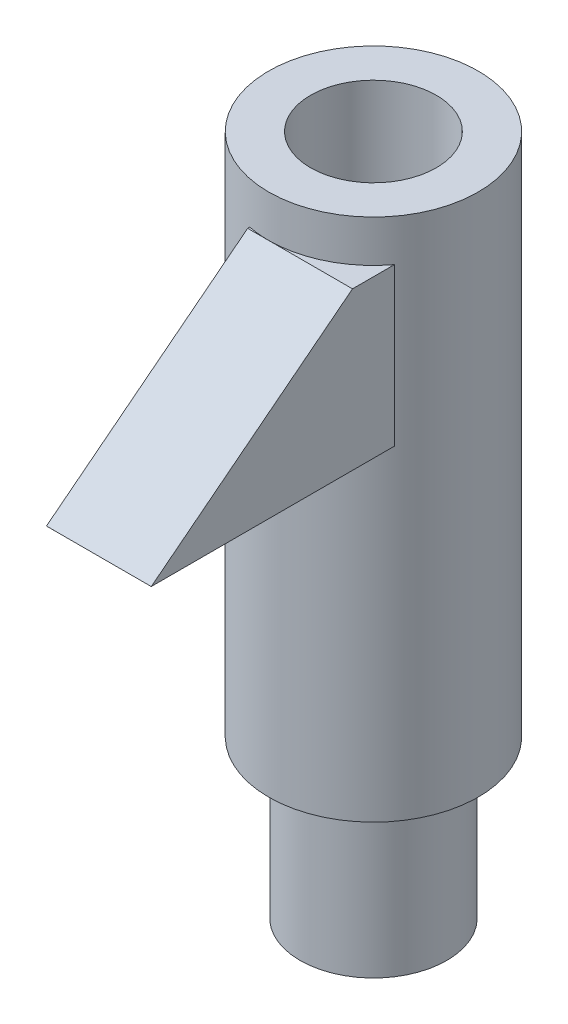
SolidWorks part; units mm, degrees
ref_plane "Alzado" through (0, 0, 0) normal (0, 0, 1) x (1, 0, 0)
ref_plane "Planta" through (0, 0, 0) normal (0, 1, 0) x (1, 0, 0)
ref_plane "Vista lateral" through (0, 0, 0) normal (1, 0, 0) x (0, 0, -1)
sketch "Croquis1" plane through (0, 0, 0) normal (0, 1, 0) x (1, 0, 0)
  circle A0 centre (0, 0) radius 7
  dimension "D1" = 14
extrude "Saliente-Extruir1" add sketch "Croquis1" along normal blind 15
sketch "Croquis2" plane through (0, 15, 0) normal (0, 1, 0) x (1, 0, 0)
  circle A0 centre (0, 0) radius 10
  dimension "D1" = 20
extrude "Saliente-Extruir2" add sketch "Croquis2" along normal blind 50
ref_plane "Plano1" through (0, 0, 10) normal (0, 0, 1) x (1, 0, 0)
sketch "Croquis3" plane through (0, 0, 10) normal (0, 0, 1) x (1, 0, 0)
  line L0 (10, 15) -> (10, 65) construction
  line L1 (-2, 46) -> (8, 46)
  line L2 (-2, 46) -> (-2, 61)
  line L3 (-2, 61) -> (8, 61)
  line L4 (8, 46) -> (8, 61)
  line L5 (-2, 46) -> (8, 61) construction
  line L6 (-2, 61) -> (8, 46) construction
  line L7 (10, 65) -> (-10, 65) construction
  point P0 (3, 53.5)
  dimension "D1" = 2
  dimension "D2" = 4
  dimension "D3" = 10
  dimension "D4" = 15
extrude "Saliente-Extruir3" add sketch "Croquis3" along normal blind 30 and the other way blind 6
chamfer "Chaflán1" distance 30 angle 38 1 edges at (3, 61, 40) first distance on face at (3.1376, 61, 24.3119)
sketch "Croquis4" plane through (0, 65, 0) normal (0, 1, 0) x (1, 0, 0)
  circle A1 centre (0, 0) radius 6
  dimension "D1" = 12
extrude "Cortar-Extruir1" cut sketch "Croquis4" against normal blind 20
